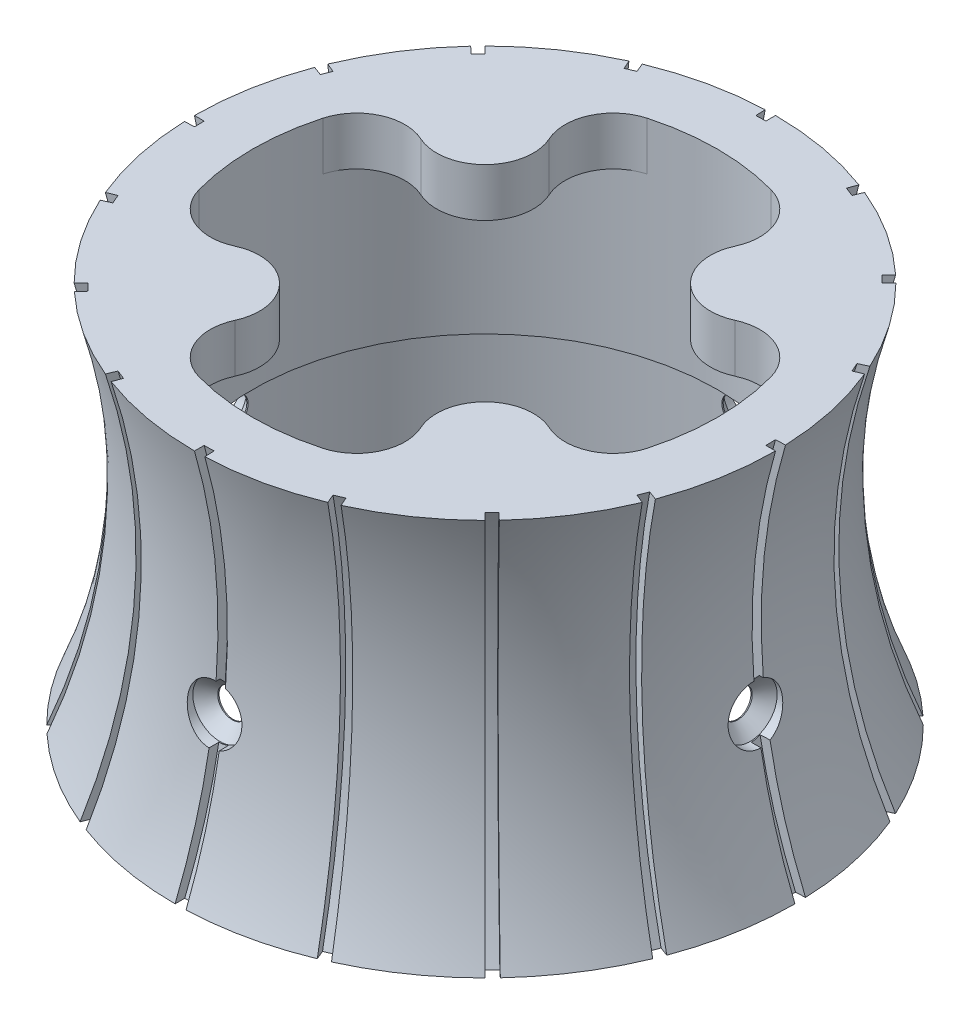
SolidWorks part; units mm, degrees
material "ABS"
ref_plane "Front Plane" through (0, 0, 0) normal (0, 0, 1) x (1, 0, 0)
ref_plane "Top Plane" through (0, 0, 0) normal (0, 1, 0) x (1, 0, 0)
ref_plane "Right Plane" through (0, 0, 0) normal (1, 0, 0) x (0, 0, -1)
sketch "Sketch1" plane through (0, 0, 0) normal (0, 0, 1) x (1, 0, 0)
  line L0 (0, 0) -> (0, 33.8642) construction
  line L1 (-23.5, 0) -> (-23.5, 19) construction
  line L2 (-23.625, 12.5) -> (-23.625, 6.5) construction
  line L3 (-23.625, 9.5) -> (-23.5, 9.5) construction
  line L4 (-26, 12.5) -> (-26, 6.5) construction
  line L5 (-26, 12.5) -> (-23.625, 12.5) construction
  line L6 (-26, 6.5) -> (-23.625, 6.5) construction
  line L9 (-23.625, 15.5) -> (-26, 15.5) construction
  line L10 (-23.625, 9.5) -> (-26, 9.5) construction
  line L17 (-24, 9.5) -> (-26, 9.5)
  line L18 (-26, 9.5) -> (-26, -8.5)
  line L19 (-26, -8.5) -> (-32, -8.5)
  line L21 (-30, 31) -> (-24, 31)
  line L22 (-24, 31) -> (-24, 9.5)
  arc A0 (-32, -8.5) -> (-30, 31) centre (-87.575, 14.1146) ccw
  dimension "D11" = 60
  dimension "D1" = 19
  dimension "D2" = 23.5
  dimension "D3" = 23.625
  dimension "D4" = 6
  dimension "D5" = 26
  dimension "D6" = 6
  dimension "D7" = 12
  dimension "D8" = 3
  dimension "D9" = 2
  dimension "D10" = 18
  dimension "D12" = 6
revolve "Revolve1" add sketch "Sketch1" angle 360 about L0
sketch "Sketch2" plane through (0, 0, 0) normal (0, 0, 1) x (1, 0, 0)
  line L0 (-26, 9.5) -> (26, 9.5) construction
  line L1 (-26, 9.5) -> (26, 9.5) construction
  circle A0 centre (0, 6.5) radius 1.5
  point P4 (0, 6.0816)
  dimension "D1" = 3
  dimension "D2" = 3
extrude "Cut-Extrude1" cut sketch "Sketch2" against normal up to next
pattern_circular "CirPattern1" count 4 over 360 about axis through (0, 0, 0) along (0, -1, 0) of "Cut-Extrude1" reverse direction yes
sketch "Sketch3" plane through (0, 31, 0) normal (0, 1, 0) x (1, 0, 0)
  line L0 (0, 0) -> (-16.9706, 16.9706) construction
  line L1 (0, 0) -> (0, 24) construction
  line L2 (-16.9706, 16.9706) -> (-21.2132, 21.2132) construction
  line L3 (-10.6066, 17.6777) -> (-13.0627, 20.1337)
  line L4 (-17.6777, 10.6066) -> (-20.1337, 13.0627)
  circle A0 centre (0, 0) radius 24 construction
  circle A1 centre (0, 0) radius 30 construction
  circle A2 centre (-14.1421, 14.1421) radius 2.5 construction
  arc A3 (-17.6777, 10.6066) -> (-10.6066, 17.6777) centre (-14.1421, 14.1421) ccw
  arc A4 (-13.0627, 20.1337) -> (-20.1337, 13.0627) centre (0, 0) ccw
  dimension "D2" = 5
  dimension "D4" = 5
  dimension "D1" = 45
  dimension "D3" = 20
extrude "Boss-Extrude1" add sketch "Sketch3" against normal blind 5
pattern_circular "CirPattern2" count 4 over 360 about axis through (0, 0, 0) along (0, -1, 0) of "Boss-Extrude1" reverse direction yes
sketch "Sketch4" plane through (0, 26, 0) normal (0, -1, 0) x (1, 0, 0)
  circle A0 centre (-14.1421, 14.1421) radius 2.5
  arc A1 (-17.6777, 10.6066) -> (-10.6066, 17.6777) centre (-14.1421, 14.1421) ccw construction
  dimension "D1" = 5
extrude "Cut-Extrude2" cut sketch "Sketch4" against normal blind 3
pattern_circular "CirPattern3" count 4 over 360 about axis through (0, 0, 0) along (0, -1, 0) of "Cut-Extrude2" reverse direction yes
fillet "Fillet2" radius 5 8 edges at (-20.1337, 28.5, 13.0627) (-13.0627, 28.5, 20.1337) (13.0627, 28.5, 20.1337) (20.1337, 28.5, 13.0627) (20.1337, 28.5, -13.0627) (13.0627, 28.5, -20.1337) (-13.0627, 28.5, -20.1337) (-20.1337, 28.5, -13.0627)
sketch "Sketch9" plane through (0, 0, 0) normal (1, 0, 0) x (0, 0, -1)
  line L0 (0, 6.5) -> (26.0685, 6.5) construction
  line L1 (0, 8) -> (0, 5)
  line L2 (0, 8) -> (0, 5) construction
  line L4 (27.7685, 6.5) -> (27.7685, 9.3) construction
  line L5 (27.7685, 6.5) -> (26.0685, 6.5)
  line L6 (27.7685, 9.3) -> (27.3685, 9.3)
  line L7 (27.3685, 9.3) -> (26.0685, 7.9743)
  line L10 (27.7685, 9.3) -> (28.5157, 9.3)
  line L11 (28.5157, 9.3) -> (28.5157, 6.5)
  line L12 (28.5157, 6.5) -> (27.7685, 6.5)
  line L13 (26.0685, 7.9743) -> (26.0685, 6.5)
  arc A1 (30, 31) -> (27.8874, 8) centre (87.575, 14.1146) ccw construction
  spline S0 degree 2 poles (26, 5) (25.9135, 6.5) (26, 8) knots 0 0 0 1 1 1 weights 0.0245 0.026 0.0275 construction
  spline S1 degree 2 poles (26, 5) (25.9135, 6.5) (26, 8) knots 0 0 0 1 1 1 weights 0.0245 0.026 0.0275 construction
  point P6 (0, 0)
  dimension "D2" = 2.8
  dimension "D3" = 1.7
  dimension "D1" = 0
revolve "Cut-Revolve2" cut sketch "Sketch9" angle 360 about L0
pattern_circular "CirPattern5" count 4 over 360 about axis through (0, 31, 0) along (0, -1, 0) of "Cut-Revolve2"
sketch "Sketch5" plane through (0, 0, 0) normal (0, 0, 1) x (1, 0, 0)
  line L0 (-30, 31) -> (-29, 31)
  line L1 (-32, -8.5) -> (-31, -8.5)
  line L2 (0, 0) -> (0, 31) construction
  line L3 (30, 31) -> (-30, 31) construction
  line L5 (-32, -8.5) -> (-26, -8.5)
  line L6 (-26, -8.5) -> (-26, 9.5)
  line L7 (-26, 9.5) -> (-24, 9.5)
  line L8 (-24, 9.5) -> (-24, 31)
  line L9 (-24, 31) -> (-30, 31)
  line L10 (-32, -8.5) -> (-26, -8.5) construction
  line L11 (-26, -8.5) -> (-26, 9.5) construction
  line L12 (-26, 9.5) -> (-24, 9.5) construction
  line L13 (-24, 9.5) -> (-24, 31) construction
  line L14 (-24, 31) -> (-30, 31) construction
  arc A0 (-29, 31) -> (-31, -8.5) centre (-86.575, 14.1146) cw
  arc A1 (-32, -8.5) -> (-30, 31) centre (-87.575, 14.1146) ccw
  arc A2 (-32, -8.5) -> (-30, 31) centre (-87.575, 14.1146) ccw
  dimension "D2" = 1
  dimension "D1" = 0
revolve "Cut-Revolve1" cut sketch "Sketch5" angle 2 about L2
pattern_circular "CirPattern4" count 16 over 360 about axis through (0, 0, 0) along (0, -1, 0) of "Cut-Revolve1" reverse direction yes
